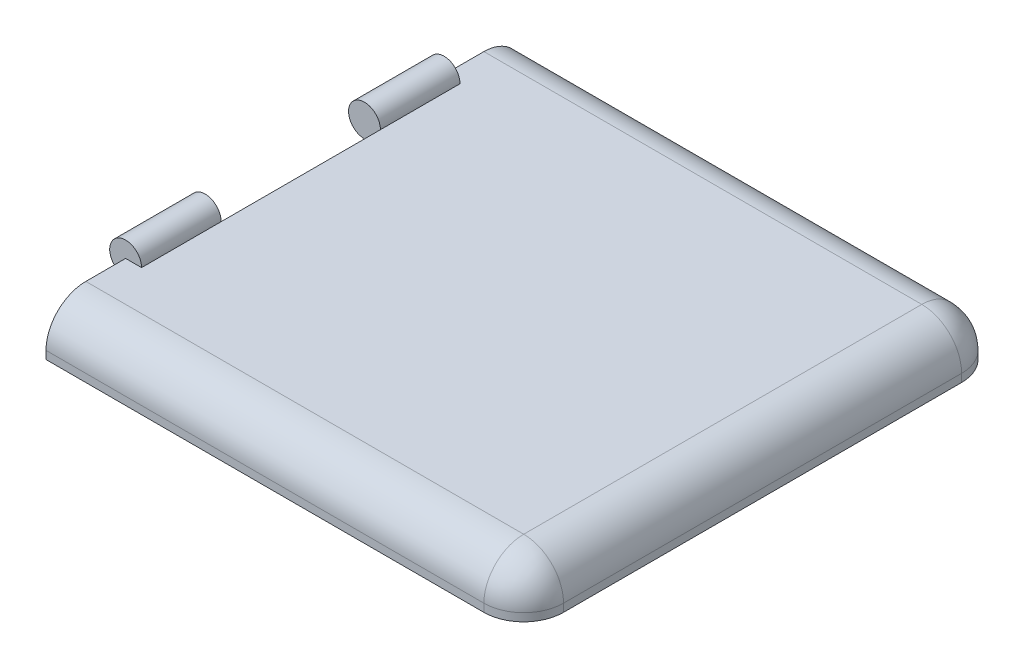
SolidWorks part; units mm, degrees
material "ABS"
ref_plane "Front" through (0, 0, 0) normal (0, 0, 1) x (1, 0, 0)
ref_plane "Top" through (0, 0, 0) normal (0, 1, 0) x (1, 0, 0)
ref_plane "Right" through (0, 0, 0) normal (1, 0, 0) x (0, 0, -1)
sketch "Sketch1" plane through (0, 0, 0) normal (0, 1, 0) x (1, 0, 0)
  line L1 (0, 0) -> (600, 0)
  line L2 (0, 0) -> (0, 600)
  line L3 (0, 600) -> (600, 600)
  line L4 (600, 0) -> (600, 600)
  dimension "D1" = 600
  dimension "D2" = 600
extrude "Boss-Extrude1" add sketch "Sketch1" along normal blind 60
ref_plane "Plane1" through (0, 0, -300) normal (0, 0, 1) x (1, 0, 0)
sketch "Sketch2" plane through (0, 0, -300) normal (0, 0, 1) x (1, 0, 0)
  circle A0 centre (0, 60) radius 20
  dimension "D1" = 40
extrude "Boss-Extrude2" add sketch "Sketch2" along normal blind 100 from offset 100
extrude "Boss-Extrude3" add sketch "Sketch2<2>" against normal blind 100 from offset 100 offset against normal yes
sketch "Sketch2<2>" plane through (0, 0, -300) normal (0, 0, 1) x (1, 0, 0) same geometry as "Sketch2"
extrude "Cut-Extrude1" cut sketch "Sketch2<3>" against normal up to surface and the other way up to surface up to face at (-1.3807, 61.3807, -400) other way up to face at (-1.3807, 61.3807, -200)
sketch "Sketch2<3>" plane through (0, 0, -300) normal (0, 0, 1) x (1, 0, 0) same geometry as "Sketch2"
fillet "Fillet1" radius 50 5 edges at (300, 60, 0) (600, 60, -300) (300, 60, -600) (600, 30, -600) (600, 30, 0)
